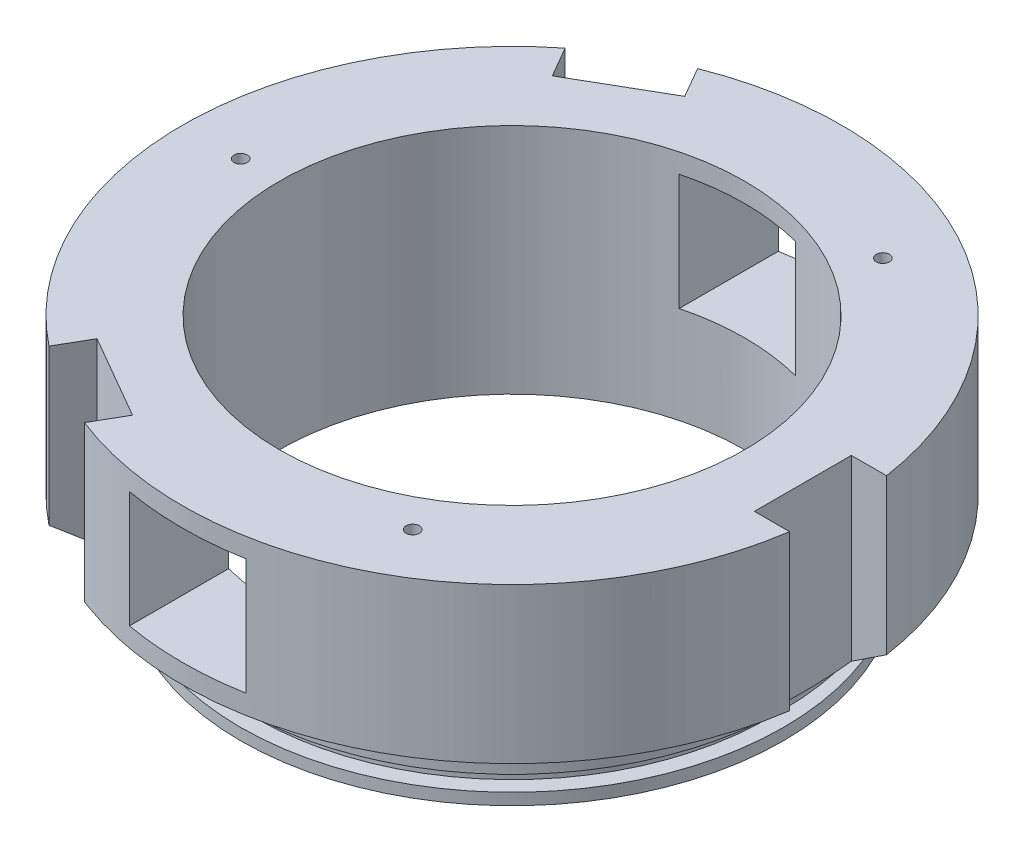
SolidWorks part; units mm, degrees
ref_plane "Front Plane" through (0, 0, 0) normal (0, 0, 1) x (1, 0, 0)
ref_plane "Top Plane" through (0, 0, 0) normal (0, 1, 0) x (1, 0, 0)
ref_plane "Right Plane" through (0, 0, 0) normal (1, 0, 0) x (0, 0, -1)
sketch "Sketch1" plane through (0, 0, 0) normal (0, 1, 0) x (1, 0, 0)
  circle A0 centre (0, 0) radius 85
  circle A1 centre (0, 0) radius 60
  dimension "D1" = 25
  dimension "D2" = 120
extrude "Boss-Extrude1" add sketch "Sketch1" along normal blind 40
ref_axis "Axis1" through (0, 0, 0) along (0, 1, 0)
ref_axis "Axis3" through (0, 0, 0) along (1, 0, 0)
sketch "Sketch4" plane through (0, 40, 0) normal (0, 1, 0) x (1, 0, 0)
  line L0 (0, 0) -> (35, -60.6218) construction
  line L1 (0, 0) -> (62.0295, 0) construction
  circle A0 centre (0, 0) radius 70 construction
  circle A1 centre (35, -60.6218) radius 1.7
  dimension "D1" = 140
  dimension "D2" = 3.4
  dimension "D3" = 60
extrude "Cut-Extrude2" cut sketch "Sketch4" against normal through all both and the other way through all
pattern_circular "CirPattern2" count 3 every 120 about axis through (0, 0, 0) along (0, 1, 0) of "Cut-Extrude2"
sketch "Sketch5" plane through (0, 40, 0) normal (0, 1, 0) x (1, 0, 0)
  line L0 (0, 0) -> (-70, 0) construction
  line L1 (0, 0) -> (0, -70) construction
  arc A0 (-70, 0) -> (0, -70) centre (0, 0) ccw
  circle A1 centre (0, 0) radius 85 construction
  point P5 (0, -72.7926)
  point P6 (0, 0)
  point P10 (0, 0)
  dimension "D1" = 90
  dimension "D2" = 70
ref_plane "Plane2" through (0, 0, 85) normal (0, 0, 1) x (1, 0, 0)
sketch "Sketch6" plane through (0, 0, 85) normal (0, 0, 1) x (1, 0, 0)
  line L1 (-15, 35) -> (15, 35)
  line L2 (-15, 35) -> (-15, 5)
  line L3 (-15, 5) -> (15, 5)
  line L4 (15, 35) -> (15, 5)
  line L6 (0, 40) -> (0, 35) construction
  point P6 (0, 35)
  dimension "D1" = 30
  dimension "D2" = 30
  dimension "D3" = 5
extrude "Cut-Extrude3" cut sketch "Sketch6" against normal through all
sketch "Sketch8" plane through (0, 0, 0) normal (1, 0, 0) x (0, 0, -1)
  line L6 (85, 0) -> (70, -10)
  line L7 (70, -10) -> (70, -13)
  line L8 (70, -20) -> (60, -20)
  line L9 (60, -20) -> (60, 0)
  line L11 (60, 0) -> (85, 0)
  line L12 (70, -17) -> (70, -20)
  line L13 (70, -13) -> (66, -13)
  line L15 (70, -17) -> (66, -17)
  line L16 (66, -13) -> (66, -17)
  point P2 (80, 0)
  point P6 (60, 0)
  point P14 (0, 0)
  point P15 (80, 0)
  point P17 (60, 0)
  point P18 (0, 0)
  point P19 (0, 0)
  dimension "D1" = 15
  dimension "D2" = 10
  dimension "D3" = 4
  dimension "D4" = 20
  dimension "D5" = 4
  dimension "D6" = 3
revolve "Revolve3" add sketch "Sketch8" angle 360 about axis through (0, 0, 0) along (0, 1, 0)
sketch "Sketch2" plane through (0, 40, 0) normal (0, 1, 0) x (1, 0, 0)
  line L0 (0, 0) -> (85, 0) construction
  line L10 (75, 12.5) -> (85, 12.5)
  line L11 (75, 12.5) -> (75, -12.5)
  line L12 (75, -12.5) -> (85, -12.5)
  line L13 (85, 12.5) -> (85, -12.5)
  circle A2 centre (0, 0) radius 85 construction
  point P1 (85, 0)
  dimension "D1" = 10
  dimension "D2" = 25
extrude "Cut-Extrude1" cut sketch "Sketch2" against normal up to surface (39.3905 mm away) up to face at (0, 0, -85)
pattern_circular "CirPattern1" count 3 every 120 about axis through (0, 0, 0) along (0, 1, 0) of "Cut-Extrude1"
